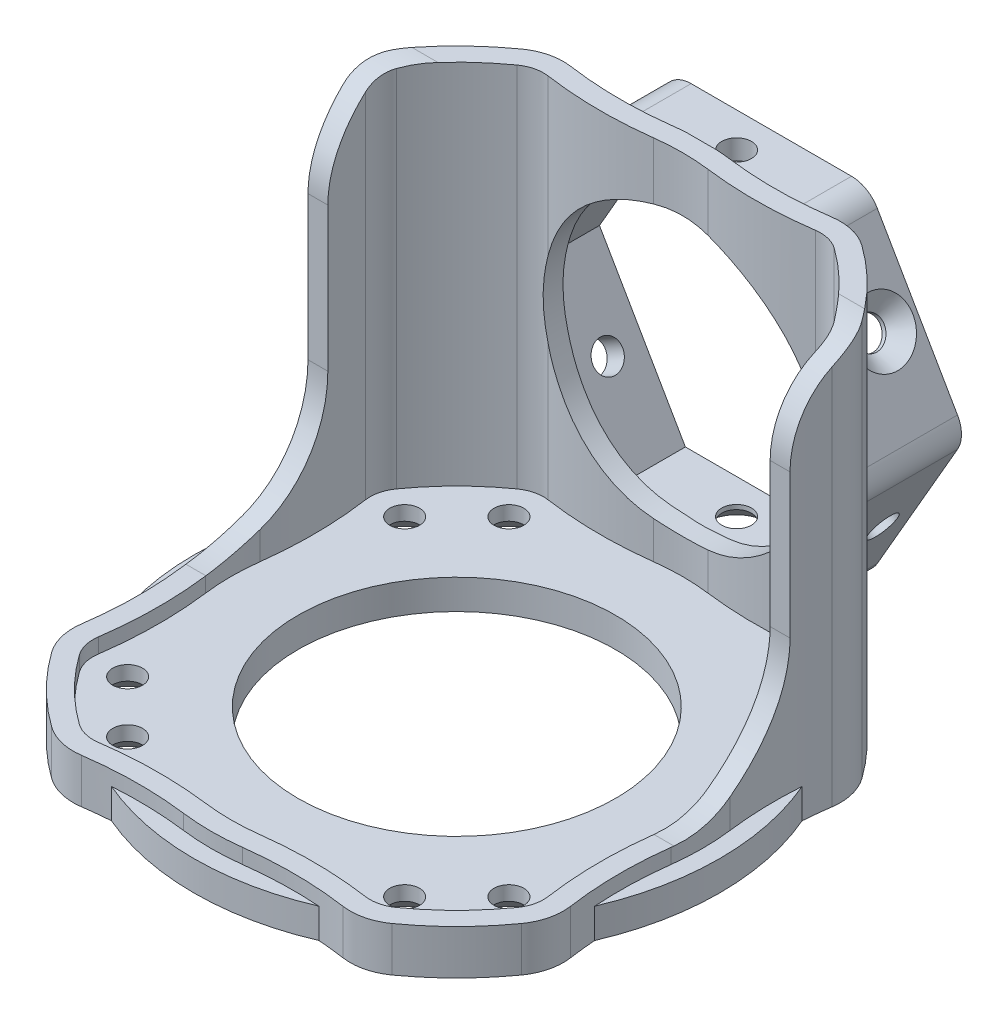
SolidWorks part; units mm, degrees
material "6061 合金"
ref_plane "前视基准面" through (0, 0, 0) normal (0, 0, 1) x (1, 0, 0)
ref_plane "上视基准面" through (0, 0, 0) normal (0, 1, 0) x (1, 0, 0)
ref_plane "右视基准面" through (0, 0, 0) normal (1, 0, 0) x (0, 0, -1)
sketch "草图1" plane through (0, 0, 0) normal (0, 1, 0) x (1, 0, 0)
  line L0 (0, 0) -> (0, 50.1956) construction
  line L1 (0, 0) -> (-38.5927, 0) construction
  line L2 (0, 0) -> (-19.2142, 13.9599) construction
  line L3 (-19.2142, 13.9599) -> (0, 0) construction
  line L4 (-13.9599, 19.2142) -> (0, 0) construction
  circle A0 centre (0, 0) radius 16
  circle A1 centre (0, 0) radius 26.5
  circle A2 centre (0, 0) radius 23.75 construction
  circle A3 centre (-19.2142, 13.9599) radius 1.5
  circle A4 centre (-13.9599, 19.2142) radius 1.5
  circle A5 centre (13.9599, 19.2142) radius 1.5
  circle A6 centre (19.2142, 13.9599) radius 1.5
  circle A7 centre (19.2142, -13.9599) radius 1.5
  circle A8 centre (13.9599, -19.2142) radius 1.5
  circle A9 centre (-19.2142, -13.9599) radius 1.5
  circle A10 centre (-13.9599, -19.2142) radius 1.5
  dimension "D1" = 32
  dimension "D2" = 47.5
  dimension "D3" = 3
  dimension "D6" = 53
  dimension "D4" = 36
  dimension "D5" = 36
extrude "凸台-拉伸1" add sketch "草图1" along normal blind 3
sketch "草图3" plane through (0, 3, 0) normal (0, 1, 0) x (1, 0, 0)
  line L0 (0, 0) -> (0, -34.5054) construction
  line L1 (0, 0) -> (28.4363, 0) construction
  line L2 (0, 0) -> (31.2107, -31.2107) construction
  arc A0 (-2.7377, -22.577) -> (2.7377, -22.577) centre (0, -1) ccw
  arc A1 (0, -21.75) -> (2.7345, -21.5774) centre (0, 0) ccw construction
  arc A2 (-2.9894, -24.5611) -> (2.9894, -24.5611) centre (0, -1) ccw
  arc A3 (2.7377, -22.577) -> (13.4637, -22.6658) centre (7.7725, -62.2589) cw
  arc A4 (13.5954, -21.6874) -> (2.7345, -21.5774) centre (7.7635, -61.26) ccw construction
  arc A5 (13.4637, -22.6658) -> (15.9902, -22.0493) centre (13.9599, -19.2142) ccw
  arc A6 (11.9599, -19.2142) -> (15.9599, -19.2142) centre (13.9599, -19.2142) ccw construction
  arc A7 (15.9902, -22.0493) -> (22.0493, -15.9902) centre (0.7071, -0.7071) ccw
  arc A8 (15.4294, -21.2367) -> (18.5616, -18.5616) centre (0, 0) ccw construction
  arc A9 (22.577, 2.7377) -> (22.577, -2.7377) centre (1, 0) cw
  arc A10 (22.577, -2.7377) -> (22.6658, -13.4637) centre (62.2589, -7.7725) ccw
  arc A11 (22.6658, -13.4637) -> (22.0493, -15.9902) centre (19.2142, -13.9599) cw
  arc A12 (-22.577, 2.7377) -> (-22.577, -2.7377) centre (-1, 0) ccw
  arc A13 (-22.577, -2.7377) -> (-22.6658, -13.4637) centre (-62.2589, -7.7725) cw
  arc A14 (-22.6658, -13.4637) -> (-22.0493, -15.9902) centre (-19.2142, -13.9599) ccw
  arc A15 (-15.9902, -22.0493) -> (-22.0493, -15.9902) centre (-0.7071, -0.7071) cw
  arc A16 (-13.4637, -22.6658) -> (-15.9902, -22.0493) centre (-13.9599, -19.2142) cw
  arc A17 (-2.7377, -22.577) -> (-13.4637, -22.6658) centre (-7.7725, -62.2589) ccw
  arc A18 (22.577, 2.7377) -> (22.6658, 13.4637) centre (62.2589, 7.7725) cw
  arc A19 (22.6658, 13.4637) -> (22.0493, 15.9902) centre (19.2142, 13.9599) ccw
  arc A20 (15.9902, 22.0493) -> (22.0493, 15.9902) centre (0.7071, 0.7071) cw
  arc A21 (13.4637, 22.6658) -> (15.9902, 22.0493) centre (13.9599, 19.2142) cw
  arc A22 (2.7377, 22.577) -> (13.4637, 22.6658) centre (7.7725, 62.2589) ccw
  arc A23 (-2.7377, 22.577) -> (2.7377, 22.577) centre (0, 1) cw
  arc A24 (-2.7377, 22.577) -> (-13.4637, 22.6658) centre (-7.7725, 62.2589) cw
  arc A25 (-13.4637, 22.6658) -> (-15.9902, 22.0493) centre (-13.9599, 19.2142) ccw
  arc A26 (-15.9902, 22.0493) -> (-22.0493, 15.9902) centre (-0.7071, 0.7071) ccw
  arc A27 (-22.6658, 13.4637) -> (-22.0493, 15.9902) centre (-19.2142, 13.9599) cw
  arc A28 (-22.577, 2.7377) -> (-22.6658, 13.4637) centre (-62.2589, 7.7725) ccw
  arc A29 (2.9894, -24.5611) -> (13.1792, -24.6455) centre (7.7725, -62.2589) cw
  arc A30 (13.1792, -24.6455) -> (17.1546, -23.6754) centre (13.9599, -19.2142) ccw
  arc A31 (17.1546, -23.6754) -> (20.6829, -20.6829) centre (0.7071, -0.7071) ccw
  arc A32 (23.6754, -17.1546) -> (20.6829, -20.6829) centre (0.7071, -0.7071) cw
  arc A33 (24.6455, -13.1792) -> (23.6754, -17.1546) centre (19.2142, -13.9599) cw
  arc A34 (24.5611, -2.9894) -> (24.6455, -13.1792) centre (62.2589, -7.7725) ccw
  arc A35 (24.5611, 2.9894) -> (24.5611, -2.9894) centre (1, 0) cw
  arc A36 (-2.9894, 24.5611) -> (2.9894, 24.5611) centre (0, 1) cw
  arc A37 (2.9894, 24.5611) -> (13.1792, 24.6455) centre (7.7725, 62.2589) ccw
  arc A38 (13.1792, 24.6455) -> (17.1546, 23.6754) centre (13.9599, 19.2142) cw
  arc A39 (17.1546, 23.6754) -> (20.6829, 20.6829) centre (0.7071, 0.7071) cw
  arc A40 (23.6754, 17.1546) -> (20.6829, 20.6829) centre (0.7071, 0.7071) ccw
  arc A41 (24.6455, 13.1792) -> (23.6754, 17.1546) centre (19.2142, 13.9599) ccw
  arc A42 (24.5611, 2.9894) -> (24.6455, 13.1792) centre (62.2589, 7.7725) cw
  arc A43 (-2.9894, -24.5611) -> (-13.1792, -24.6455) centre (-7.7725, -62.2589) ccw
  arc A44 (-13.1792, -24.6455) -> (-17.1546, -23.6754) centre (-13.9599, -19.2142) cw
  arc A45 (-17.1546, -23.6754) -> (-20.6829, -20.6829) centre (-0.7071, -0.7071) cw
  arc A46 (-23.6754, -17.1546) -> (-20.6829, -20.6829) centre (-0.7071, -0.7071) ccw
  arc A47 (-24.6455, -13.1792) -> (-23.6754, -17.1546) centre (-19.2142, -13.9599) ccw
  arc A48 (-24.5611, -2.9894) -> (-24.6455, -13.1792) centre (-62.2589, -7.7725) cw
  arc A49 (-24.5611, 2.9894) -> (-24.5611, -2.9894) centre (-1, 0) ccw
  arc A50 (-24.5611, 2.9894) -> (-24.6455, 13.1792) centre (-62.2589, 7.7725) ccw
  arc A51 (-24.6455, 13.1792) -> (-23.6754, 17.1546) centre (-19.2142, 13.9599) cw
  arc A52 (-23.6754, 17.1546) -> (-20.6829, 20.6829) centre (-0.7071, 0.7071) cw
  arc A53 (-17.1546, 23.6754) -> (-20.6829, 20.6829) centre (-0.7071, 0.7071) ccw
  arc A54 (-13.1792, 24.6455) -> (-17.1546, 23.6754) centre (-13.9599, 19.2142) ccw
  arc A55 (-2.9894, 24.5611) -> (-13.1792, 24.6455) centre (-7.7725, 62.2589) cw
  point P11 (14.7866, -22.6019)
  point P18 (0, -21.75)
  point P32 (18.5616, -18.5616)
  point P41 (22.6019, -14.7866)
  point P49 (-14.7866, -22.6019)
  point P79 (18.9801, -22.2515)
  point P82 (22.2515, -18.9801)
extrude "凸台-拉伸2" add sketch "草图3" along normal blind 37 and the other way blind 3
sketch "草图4" plane through (0, 0, 0) normal (1, 0, 0) x (0, 0, -1)
  line L0 (-27.9047, 4.5) -> (-2.7066, 4.5)
  line L1 (9.2934, 16.5) -> (9.2934, 31)
  line L2 (18.2934, 40) -> (24.7013, 40)
  line L3 (13.1792, 40) -> (2.9894, 40) construction
  line L4 (24.7013, 40) -> (24.7013, -2.0238)
  line L5 (24.7013, 0) -> (24.7013, 40) construction
  line L6 (-27.9047, 4.5) -> (-27.9047, 47.0536)
  line L7 (-27.9047, 47.0536) -> (30.5436, 47.0536)
  line L8 (30.5436, 47.0536) -> (30.5436, -2.0238)
  line L9 (30.5436, -2.0238) -> (24.7013, -2.0238)
  line L10 (-24.3532, 3) -> (-26.5, 3) construction
  arc A0 (-2.7066, 4.5) -> (9.2934, 16.5) centre (-2.7066, 16.5) ccw
  arc A1 (9.2934, 31) -> (18.2934, 40) centre (18.2934, 31) cw
  dimension "D1" = 12
  dimension "D2" = 9
  dimension "D3" = 1.5
extrude "切除-拉伸1" cut sketch "草图4" against normal through all and the other way through all
sketch "草图5" plane through (0, 0, -24.7013) normal (0, 0, -1) x (-1, 0, 0)
  line L0 (0, 12.6) -> (0, 40.3) construction
  line L1 (9.5966, 3) -> (1.5201, 3) construction
  circle A0 centre (0, 20.5) radius 14
  circle A1 centre (0, 20.5) radius 17.5 construction
  dimension "D1" = 28
  dimension "D2" = 35
extrude "切除-拉伸2" cut sketch "草图5" against normal blind 45
sketch "草图6" plane through (0, 40, 0) normal (0, 1, 0) x (1, 0, 0)
  line L0 (-13.1792, 24.6455) -> (-10.4923, 27.3324)
  line L1 (-10.4923, 27.3324) -> (-4.7068, 27.3324)
  line L2 (-4.7068, 27.3324) -> (-1.5201, 24.7013)
  line L3 (1.5201, 24.7013) -> (2.7707, 27.3324)
  line L4 (2.7707, 27.3324) -> (10.4432, 27.0412)
  line L5 (10.4432, 27.0412) -> (13.1792, 24.6455)
  arc A0 (1.5201, 24.7013) -> (2.9894, 24.5611) centre (0, 1) cw
  arc A1 (2.9894, 24.5611) -> (13.1792, 24.6455) centre (7.7725, 62.2589) ccw
  arc A2 (-1.5201, 24.7013) -> (-2.9894, 24.5611) centre (0, 1) ccw
  arc A3 (-2.9894, 24.5611) -> (-13.1792, 24.6455) centre (-7.7725, 62.2589) cw
extrude "切除-拉伸3" cut sketch "草图6" against normal blind 45
sketch "草图7" plane through (0, 0, -24.7013) normal (0, 0, -1) x (-1, 0, 0)
  line L1 (8.6603, 5.5) -> (17.3205, 20.5)
  line L2 (17.3205, 20.5) -> (8.6603, 35.5)
  line L3 (8.6603, 35.5) -> (-8.6603, 35.5)
  line L4 (-8.6603, 35.5) -> (-17.3205, 20.5)
  line L5 (-17.3205, 20.5) -> (-8.6603, 5.5)
  line L6 (-8.6603, 5.5) -> (8.6603, 5.5)
  line L7 (10.681, 5) -> (18.7639, 19)
  line L8 (18.7639, 22) -> (10.681, 36)
  line L9 (8.0829, 37.5) -> (-8.0829, 37.5)
  line L10 (-10.681, 36) -> (-18.7639, 22)
  line L11 (-18.7639, 19) -> (-10.681, 5)
  line L12 (-8.0829, 3.5) -> (8.0829, 3.5)
  circle A0 centre (0, 20.5) radius 15 construction
  arc A1 (13.1792, 25.2233) -> (2.9894, 34.1771) centre (0, 20.5) ccw construction
  circle A2 centre (0, 20.5) radius 17 construction
  arc A3 (10.681, 36) -> (8.0829, 37.5) centre (8.0829, 34.5) ccw
  arc A4 (18.7639, 19) -> (18.7639, 22) centre (16.1658, 20.5) ccw
  arc A5 (10.681, 5) -> (8.0829, 3.5) centre (8.0829, 6.5) cw
  arc A6 (-10.681, 5) -> (-8.0829, 3.5) centre (-8.0829, 6.5) ccw
  arc A7 (-18.7639, 22) -> (-18.7639, 19) centre (-16.1658, 20.5) ccw
  arc A8 (-8.0829, 37.5) -> (-10.681, 36) centre (-8.0829, 34.5) ccw
  dimension "D1" = 30
  dimension "D2" = 34
  dimension "D3" = 3
extrude "凸台-拉伸3" add sketch "草图7" along normal blind 7 and the other way blind 6
sketch "草图8" plane through (0, 40, 0) normal (0, 1, 0) x (1, 0, 0)
  line L0 (-22.0493, 15.9902) -> (22.0493, 15.9902)
  arc A0 (-22.0493, 15.9902) -> (-15.9902, 22.0493) centre (-0.7071, 0.7071) cw
  arc A1 (-15.9902, 22.0493) -> (-13.4637, 22.6658) centre (-13.9599, 19.2142) cw
  arc A2 (-13.4637, 22.6658) -> (-2.7377, 22.577) centre (-7.7725, 62.2589) ccw
  arc A3 (-2.7377, 22.577) -> (2.7377, 22.577) centre (0, 1) cw
  arc A4 (2.7377, 22.577) -> (13.4637, 22.6658) centre (7.7725, 62.2589) ccw
  arc A5 (13.4637, 22.6658) -> (15.9902, 22.0493) centre (13.9599, 19.2142) cw
  arc A6 (15.9902, 22.0493) -> (22.0493, 15.9902) centre (0.7071, 0.7071) cw
extrude "切除-拉伸4" cut sketch "草图8" against normal up to surface (37 mm away) up to face at (0, 3, 24.9493)
sketch "草图9" plane through (5.8457, -3.375, 0) normal (0.866, -0.5, 0) x (0, 0, -1)
  line L0 (31.7013, 17.7535) -> (28.2013, 17.7535) construction
  line L1 (31.7013, 25.8364) -> (31.7013, 9.6706) construction
  circle A0 centre (28.2013, 17.7535) radius 1.5
  dimension "D2" = 3
  dimension "D1" = 3.5
sketch "草图10" plane through (23.5992, 13.625, 0) normal (0.866, 0.5, 0) x (0, 0, -1)
  line L0 (31.7013, 17.7535) -> (28.2013, 17.7535) construction
  line L1 (31.7013, 25.8364) -> (31.7013, 9.6706) construction
  circle A0 centre (28.2013, 17.7535) radius 1.5
  dimension "D2" = 3
  dimension "D1" = 3.5
sketch "草图11" plane through (0, 37.5, 0) normal (0, 1, 0) x (1, 0, 0)
  line L0 (0, 31.7013) -> (0, 28.2013) construction
  line L1 (-8.0829, 31.7013) -> (8.0829, 31.7013) construction
  circle A0 centre (0, 28.2013) radius 1.5
  dimension "D2" = 3
  dimension "D1" = 3.5
extrude "切除-拉伸5" cut sketch "草图9" against normal through all
extrude "切除-拉伸6" cut sketch "草图10" against normal through all
extrude "切除-拉伸7" cut sketch "草图11" against normal through all
sketch "草图13" plane through (0, 0, 0) normal (0, -1, 0) x (1, 0, 0)
  line L0 (-15.3414, 23.7705) -> (-23.8773, 15.2346)
  line L1 (-23.8773, 15.2346) -> (-23.8773, 12.4211)
  line L2 (-23.8773, 12.4211) -> (-21.9936, 13.351)
  line L3 (-21.9936, 13.351) -> (-19.6093, 16.856)
  line L4 (-19.6093, 16.856) -> (-16.2117, 20.2536)
  line L5 (-16.2117, 20.2536) -> (-13.2745, 21.7036)
  line L6 (-13.2745, 21.7036) -> (-13.2745, 23.7705)
  line L7 (-13.2745, 23.7705) -> (-15.3414, 23.7705)
  line L8 (-23.5434, -13.1387) -> (-22.5897, -16.8106)
  line L9 (-22.5897, -16.8106) -> (-20.8015, -19.5287)
  line L10 (-20.8015, -19.5287) -> (-18.7152, -21.615)
  line L11 (-18.7152, -21.615) -> (-16.2117, -22.8667)
  line L12 (-16.2117, -22.8667) -> (-13.9895, -23.9778)
  line L13 (-13.9895, -23.9778) -> (-12.6233, -23.9778)
  line L14 (-12.6233, -23.9778) -> (-12.6233, -21.615)
  line L15 (-12.6233, -21.615) -> (-14.7431, -21.2454)
  line L16 (-14.7431, -21.2454) -> (-16.5444, -19.4441)
  line L17 (-16.5444, -19.4441) -> (-20.5318, -15.4567)
  line L18 (-20.5318, -15.4567) -> (-23.0666, -11.6038)
  line L19 (-23.0666, -11.6038) -> (-23.5434, -13.1387)
  line L20 (12.4234, -21.615) -> (13.0371, -23.9778)
  line L21 (13.0371, -23.9778) -> (15.8427, -23.2491)
  line L22 (15.8427, -23.2491) -> (19.6712, -20.7304)
  line L23 (19.6712, -20.7304) -> (22.1674, -17.4504)
  line L24 (22.1674, -17.4504) -> (23.4074, -14.9705)
  line L25 (23.4074, -14.9705) -> (23.4074, -13.5303)
  line L26 (23.4074, -13.5303) -> (21.8812, -13.0561)
  line L27 (21.8812, -13.0561) -> (20.6809, -15.4567)
  line L28 (20.6809, -15.4567) -> (18.9107, -17.2269)
  line L29 (18.9107, -17.2269) -> (16.7251, -19.0904)
  line L30 (16.7251, -19.0904) -> (15.1672, -20.6483)
  line L31 (15.1672, -20.6483) -> (13.6978, -21.615)
  line L32 (13.6978, -21.615) -> (12.4234, -21.615)
  line L33 (12.4234, 23.0972) -> (13.4832, 22.0374)
  line L34 (13.4832, 22.0374) -> (15.4588, 20.5339)
  line L35 (15.4588, 20.5339) -> (17.0571, 19.3175)
  line L36 (17.0571, 19.3175) -> (18.1598, 17.6413)
  line L37 (18.1598, 17.6413) -> (19.5861, 16.215)
  line L38 (19.5861, 16.215) -> (20.3097, 14.9845)
  line L39 (20.3097, 14.9845) -> (22.0095, 13.6908)
  line L40 (22.0095, 13.6908) -> (23.0963, 12.8638)
  line L41 (23.0963, 12.8638) -> (23.5689, 15.575)
  line L42 (23.5689, 15.575) -> (21.9203, 18.3788)
  line L43 (21.9203, 18.3788) -> (19.0885, 20.5339)
  line L44 (19.0885, 20.5339) -> (16.7251, 22.3326)
  line L45 (16.7251, 22.3326) -> (14.7606, 23.3148)
  line L46 (14.7606, 23.3148) -> (12.4234, 23.0972)
  circle A0 centre (19.2142, 13.9599) radius 1.5 construction
extrude "凸台-拉伸4" add sketch "草图13" against normal blind 3
chamfer "倒角1" distance 1.55 angle 45 8 edges at (19.2142, 0, -15.4599) (13.9599, 0, -20.7142) (-13.9599, 0, -17.7142) (-19.2142, 0, -12.4599) (-19.2142, 0, 12.4599) (-13.9599, 0, 17.7142) (19.2142, 0, 15.4599) (13.9599, 0, 20.7142)
chamfer "倒角2" distance 1.55 angle 45 3 edges at (-15.4724, 27.701, -28.2013) (13.9724, 30.299, -28.2013) (0, 3.5, -29.7013)
